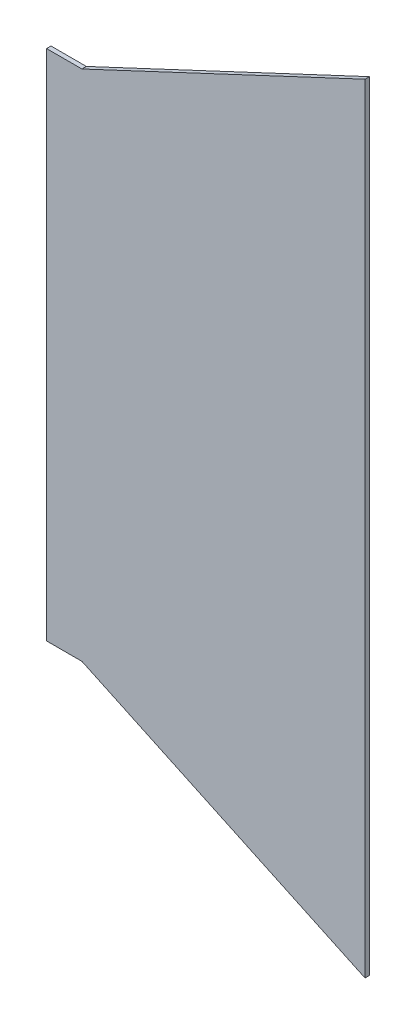
SolidWorks part; units mm, degrees
ref_plane "Front Plane" through (0, 0, 0) normal (1, 0, 0) x (0, 1, 0)
ref_plane "Top Plane" through (0, 0, 0) normal (0, 0, 1) x (0, 1, 0)
ref_plane "Right Plane" through (0, 0, 0) normal (0, 1, 0) x (-1, 0, 0)
sketch "Sketch1" plane through (0, 0, 0) normal (0, 0, 1) x (0, 1, 0)
  line L0 (-368.3, -25.4) -> (-368.3, 0)
  line L1 (-368.3, 0) -> (0, 0)
  line L2 (0, 0) -> (0, -25.4)
  line L3 (-368.3, -25.4) -> (-463.55, -228.6)
  line L4 (-463.55, -228.6) -> (95.25, -228.6)
  line L5 (95.25, -228.6) -> (0, -25.4)
  point P2 (-184.15, -228.6)
  point P7 (-184.15, 0)
  dimension "D1" = 368.3
  dimension "D2" = 25.4
  dimension "D3" = 558.8
  dimension "D4" = 203.2
extrude "Boss-Extrude1" add sketch "Sketch1" along normal blind 3.175
